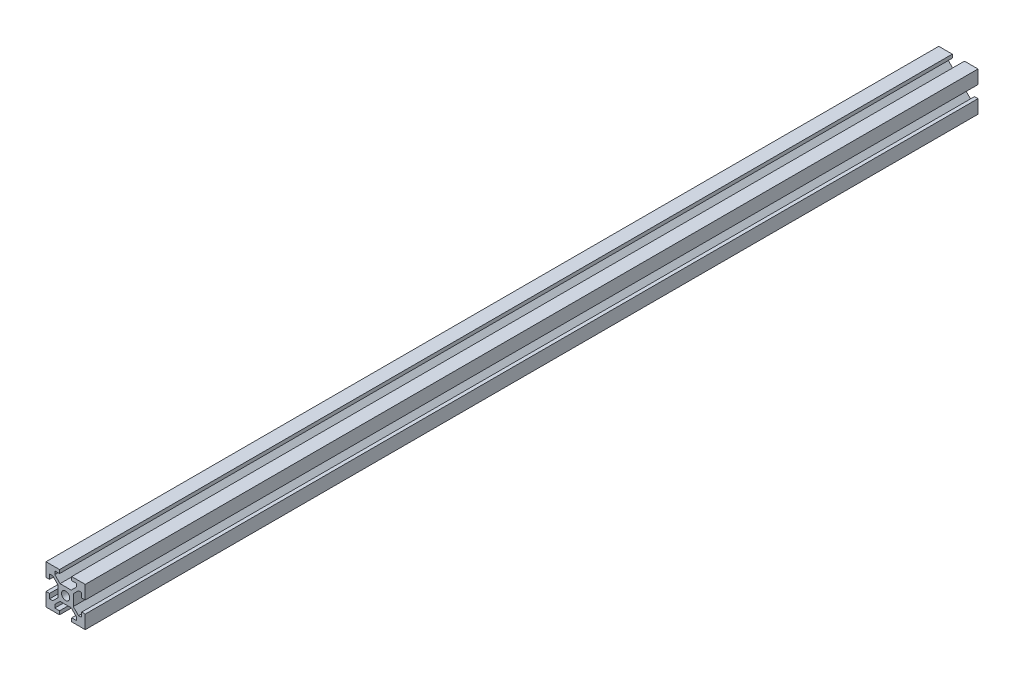
SolidWorks part; units mm, degrees
ref_plane "Front Plane" through (0, 0, 0) normal (0, 0, 1) x (1, 0, 0)
ref_plane "Top Plane" through (0, 0, 0) normal (0, 1, 0) x (1, 0, 0)
ref_plane "Right Plane" through (0, 0, 0) normal (1, 0, 0) x (0, 0, -1)
sketch "Sketch1" plane through (0, 0, 0) normal (0, 0, 1) x (1, 0, 0)
  line L0 (-3.1, 10) -> (-3.1, 8.2007)
  line L1 (-10, 10) -> (-3.1, 10)
  line L2 (-10, 10) -> (-10, 3.1)
  line L3 (-10, -10) -> (-3.1, -10)
  line L4 (10, 10) -> (10, 3.1)
  line L5 (-10, 10) -> (10, -10) construction
  line L6 (-10, -10) -> (10, 10) construction
  line L7 (-3.1, 8.2007) -> (-5.5, 8.2007)
  line L8 (-5.5, 8.2007) -> (-5.5, 6.5607)
  line L9 (-5.5, 6.5607) -> (-2.84, 3.9007)
  line L10 (-2.84, 3.9007) -> (2.84, 3.9007)
  line L11 (2.84, 3.9007) -> (5.5, 6.5607)
  line L12 (5.5, 6.5607) -> (5.5, 8.2007)
  line L13 (5.5, 8.2007) -> (3.1, 8.2007)
  line L14 (3.1, 8.2007) -> (3.1, 10)
  line L15 (-3.1, 8.2007) -> (3.1, 8.2007) construction
  line L16 (-5.5, 6.5607) -> (5.5, 6.5607) construction
  line L17 (3.1, 10) -> (10, 10)
  line L18 (8.2007, 3.1) -> (8.2007, 5.5)
  line L19 (8.2007, 5.5) -> (6.5607, 5.5)
  line L20 (6.5607, 5.5) -> (3.9007, 2.84)
  line L21 (3.9007, 2.84) -> (3.9007, -2.84)
  line L22 (3.9007, -2.84) -> (6.5607, -5.5)
  line L23 (6.5607, -5.5) -> (8.2007, -5.5)
  line L24 (8.2007, -5.5) -> (8.2007, -3.1)
  line L25 (8.2007, 3.1) -> (8.2007, -3.1) construction
  line L26 (6.5607, 5.5) -> (6.5607, -5.5) construction
  line L27 (10, 3.1) -> (8.2007, 3.1)
  line L28 (8.2007, -3.1) -> (10, -3.1)
  line L29 (3.1, -8.2007) -> (5.5, -8.2007)
  line L30 (5.5, -8.2007) -> (5.5, -6.5607)
  line L31 (5.5, -6.5607) -> (2.84, -3.9007)
  line L32 (2.84, -3.9007) -> (-2.84, -3.9007)
  line L33 (-2.84, -3.9007) -> (-5.5, -6.5607)
  line L34 (-5.5, -6.5607) -> (-5.5, -8.2007)
  line L35 (-5.5, -8.2007) -> (-3.1, -8.2007)
  line L36 (3.1, -8.2007) -> (-3.1, -8.2007) construction
  line L37 (5.5, -6.5607) -> (-5.5, -6.5607) construction
  line L38 (3.1, -10) -> (3.1, -8.2007)
  line L39 (-3.1, -8.2007) -> (-3.1, -10)
  line L40 (-8.2007, -3.1) -> (-8.2007, -5.5)
  line L41 (-8.2007, -5.5) -> (-6.5607, -5.5)
  line L42 (-6.5607, -5.5) -> (-3.9007, -2.84)
  line L43 (-3.9007, -2.84) -> (-3.9007, 2.84)
  line L44 (-3.9007, 2.84) -> (-6.5607, 5.5)
  line L45 (-6.5607, 5.5) -> (-8.2007, 5.5)
  line L46 (-8.2007, 5.5) -> (-8.2007, 3.1)
  line L47 (-8.2007, -3.1) -> (-8.2007, 3.1) construction
  line L48 (-6.5607, -5.5) -> (-6.5607, 5.5) construction
  line L49 (-10, -3.1) -> (-8.2007, -3.1)
  line L50 (-8.2007, 3.1) -> (-10, 3.1)
  line L51 (10, -3.1) -> (10, -10)
  line L52 (3.1, -10) -> (10, -10)
  line L53 (-10, -3.1) -> (-10, -10)
  point P0 (0, 0)
  point P8 (0, 8.2007)
  point P18 (0, 3.9007)
  dimension "D1" = 20
  dimension "D2" = 20
  dimension "D3" = 5.68
  dimension "D4" = 6.2
  dimension "D5" = 4.3
  dimension "D6" = 11
  dimension "D7" = 0.75
  dimension "D8" = 4
extrude "Boss-Extrude1" add sketch "Sketch1" along normal blind 454.97
sketch "Sketch2" plane through (0, 0, 454.97) normal (0, 0, 1) x (1, 0, 0)
  circle A0 centre (0, 0) radius 2.1
  dimension "D1" = 4.2
extrude "Cut-Extrude1" cut sketch "Sketch2" against normal through all
sketch "Sketch3" plane through (0, 3.9007, 0) normal (0, 1, 0) x (1, 0, 0)
  line L0 (0, 0) -> (0, -454.97) construction
  line L1 (2.84, -454.97) -> (-2.84, -454.97) construction
  circle A0 centre (0, -227.485) radius 2.1
  dimension "D1" = 4.2
extrude "Cut-Extrude2" cut sketch "Sketch3" against normal through all
